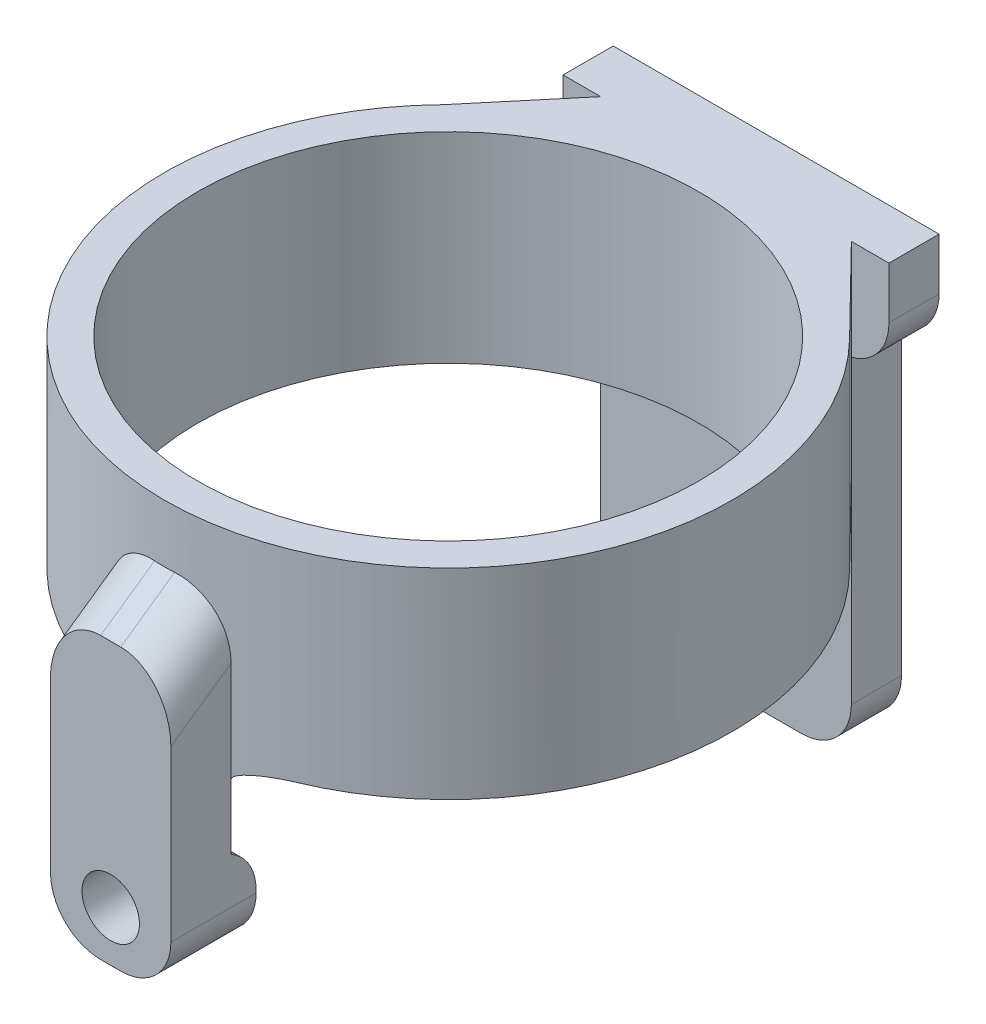
SolidWorks part; units mm, degrees
ref_plane "Ebene vorne" through (0, 0, 0) normal (0, 0, 1) x (1, 0, 0)
ref_plane "Ebene oben" through (0, 0, 0) normal (0, 1, 0) x (1, 0, 0)
ref_plane "Ebene rechts" through (0, 0, 0) normal (1, 0, 0) x (0, 0, -1)
sketch "Skizze1" plane through (0, 0, 0) normal (0, 0, 1) x (1, 0, 0)
  line L1 (0, 0) -> (12, 0)
  line L2 (0, 0) -> (0, -10)
  line L3 (0, -10) -> (12, -10)
  line L4 (12, 0) -> (12, -10)
  dimension "D1" = 12
  dimension "D2" = 10
extrude "Halterungssockel" add sketch "Skizze1" along normal blind 2
sketch "Skizze2" plane through (0, 0, 2) normal (0, 0, 1) x (1, 0, 0)
  line L9 (-7.1018, 10) -> (17.8982, 10)
  line L10 (-7.1018, 10) -> (-7.1018, -25)
  line L11 (-7.1018, -25) -> (17.8982, -25)
  line L12 (17.8982, 10) -> (17.8982, -25)
  dimension "D1" = 25
  dimension "D2" = 35
  dimension "D3" = 10
extrude "Aufsatz-Linear austragen2" add sketch "Skizze2" along normal blind 5
sketch "Skizze3" plane through (0, 0, 0) normal (0, 0, -1) x (-1, 0, 0)
  circle A0 centre (-5.1084, -15) radius 3
  dimension "D2" = 6
  dimension "D1" = 15
extrude "Schnitt-Linear austragen1" cut sketch "Skizze3" against normal through all and the other way through all contours A0
ref_plane "Ebene2" through (17.8982, 10, 7) normal (-1, 0, 0) x (0, 0, 1)
sketch "Skizze7" plane through (0, 10, 0) normal (0, 1, 0) x (1, 0, 0)
  line L0 (6, -2) -> (6, -35.3069) construction
  line L1 (12, -2) -> (0, -2) construction
  line L2 (26.2235, -15.5005) -> (17.8982, -7)
  line L3 (17.8982, -0.125) -> (17.8982, -13.875) construction
  line L4 (17.8982, -7) -> (-7.1018, -7) construction
  line L5 (17.8982, -7) -> (-7.1018, -7)
  line L7 (-14.2235, -15.5005) -> (-7.1018, -7)
  circle A0 centre (6, -35.3069) radius 25
  arc A1 (-14.2235, -15.5005) -> (26.2235, -15.5005) centre (6, -35.3069) ccw
  dimension "D1" = 50
extrude "Aufsatz-Linear austragen3" add sketch "Skizze7" against normal mid plane 20
sketch "Skizze8" plane through (0, 0, 7) normal (0, 0, -1) x (-1, 0, 0)
  line L6 (10.8518, 10) -> (-21.6482, 10)
  line L7 (7.1018, 20) -> (14.2235, 20) construction
  line L8 (10.6626, 20) -> (-26.2235, 20) construction
  line L9 (-26.2235, 20) -> (-26.2235, 10) construction
  line L10 (-26.2235, 0) -> (-26.2235, 20) construction
  line L11 (-26.2235, 10) -> (12.2679, 10) construction
  line L12 (12.2679, 10) -> (12.2679, 20) construction
  line L13 (12.2679, 20) -> (-26.2235, 20) construction
  line L14 (10.8518, 10) -> (10.8518, 20)
  line L15 (10.8518, 20) -> (-21.6482, 20)
  line L16 (-21.6482, 10) -> (-21.6482, 20)
  dimension "D1" = 10
  dimension "D2" = 32.5
  dimension "D3" = 3.75
extrude "Aufsatz-Linear austragen4" add sketch "Skizze8" along normal blind 5
ref_plane "Ebene3" through (0, 0, 0) normal (0, -1, 0) x (-1, 0, 0)
sketch "Skizze13" plane through (0, 0, 0) normal (0, -1, 0) x (-1, 0, 0)
  line L0 (0, 0) -> (0, -76.891) construction
  line L6 (-12, 0) -> (-12, -76.891) construction
  line L7 (-12, -76.891) -> (0, -76.891) construction
  line L8 (-12, -62.9707) -> (0, -62.9707)
  line L9 (-12, -62.9707) -> (-12, -68.9707)
  line L10 (-12, -68.9707) -> (0, -68.9707)
  line L11 (0, -62.9707) -> (0, -68.9707)
  arc A1 (-26.2235, -15.5005) -> (14.2235, -15.5005) centre (-6, -35.3069) ccw construction
  dimension "D1" = 6
extrude "Aufsatz-Linear austragen6" add sketch "Skizze13" against normal mid plane 35
chamfer "Fase1" distance 10 angle 35 1 edges at (6, 17.5, 68.9707) first distance on face at (6, 17.5, 66.1315)
fillet "Verrundung9" radius 1.5 2 edges at (5.3982, 0, 7) (6, 0, 62.9707)
sketch "Skizze16" plane through (0, 0, 62.9707) normal (0, 0, -1) x (-1, 0, 0)
  line L0 (0, -7.8968) -> (-12, -7.8968)
  line L4 (0, -17.5) -> (0, -1.5)
  line L5 (0, -1.5) -> (-12, -1.5)
  line L6 (-12, -1.5) -> (-12, -17.5)
  line L7 (-12, -17.5) -> (0, -17.5)
  line L8 (0, -17.5) -> (0, -7.8968)
  line L10 (-12, -7.8968) -> (-12, -17.5)
  line L11 (-12, -17.5) -> (0, -17.5)
  dimension "D1" = 0
extrude "Aufsatz-Linear austragen8" add sketch "Skizze16" along normal blind 2.5
fillet "Verrundung10" radius 5 9 edges at (6, -7.8968, 60.4707) (-10.8518, 10, 4.5) (-7.1018, -25, 4.5) (17.8982, -25, 4.5) (21.6482, 10, 4.5) (0, 12.5985, 65.9707) (12, 12.5985, 65.9707) (0, -17.5, 64.7207) (12, -17.5, 64.7207)
sketch "Skizze17" plane through (0, 0, 68.9707) normal (0, 0, 1) x (1, 0, 0)
  line L0 (6, -17.5) -> (6, -7.5) construction
  line L1 (7, -17.5) -> (5, -17.5) construction
  line L2 (6, -7.5) -> (6, -12.5) construction
  line L3 (6, -12.5) -> (12, -12.5) construction
  line L4 (12, 4.3941) -> (12, -12.5) construction
  line L5 (12, -12.5) -> (0, -12.5) construction
  line L6 (0, 4.3941) -> (0, -12.5) construction
  circle A1 centre (6, -12.5) radius 2.8657
  dimension "D1" = 5
extrude "Schnitt-Linear austragen2" cut sketch "Skizze17" against normal blind 10
chamfer "Fase2" distance 0.5 angle 45 8 edges at (6, -10, 0) (12, -10, 1) (12, -5, 0) (12, 0, 1) (6, 0, 0) (0, 0, 1) (0, -5, 0) (0, -10, 1)
